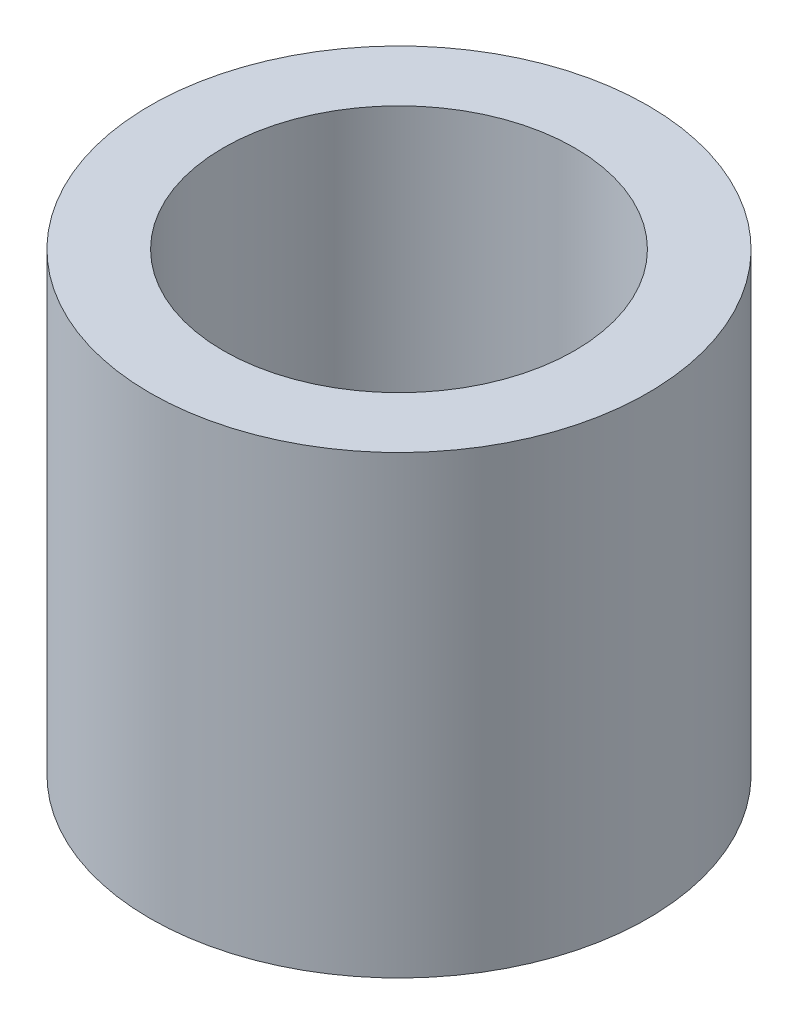
SolidWorks part; units mm, degrees
ref_plane "Front Plane" through (0, 0, 0) normal (0, 0, 1) x (1, 0, 0)
ref_plane "Top Plane" through (0, 0, 0) normal (0, 1, 0) x (1, 0, 0)
ref_plane "Right Plane" through (0, 0, 0) normal (1, 0, 0) x (0, 0, -1)
sketch "Sketch1" plane through (0, 0, 0) normal (0, 1, 0) x (1, 0, 0)
  circle A0 centre (0, 0) radius 32.5
  dimension "SLEEVE_OD" = 65
extrude "Boss-Extrude1" add sketch "Sketch1" along normal blind 59.4069
sketch "Sketch2" plane through (0, 0, 0) normal (0, 1, 0) x (1, 0, 0)
  circle A0 centre (0, 0) radius 22.933
  dimension "BORE_D" = 45.8659
extrude "Cut-Extrude1" cut sketch "Sketch2" along normal through all
chamfer "Chamfer1" distance 3.5151 angle 60 rebuild error yes
